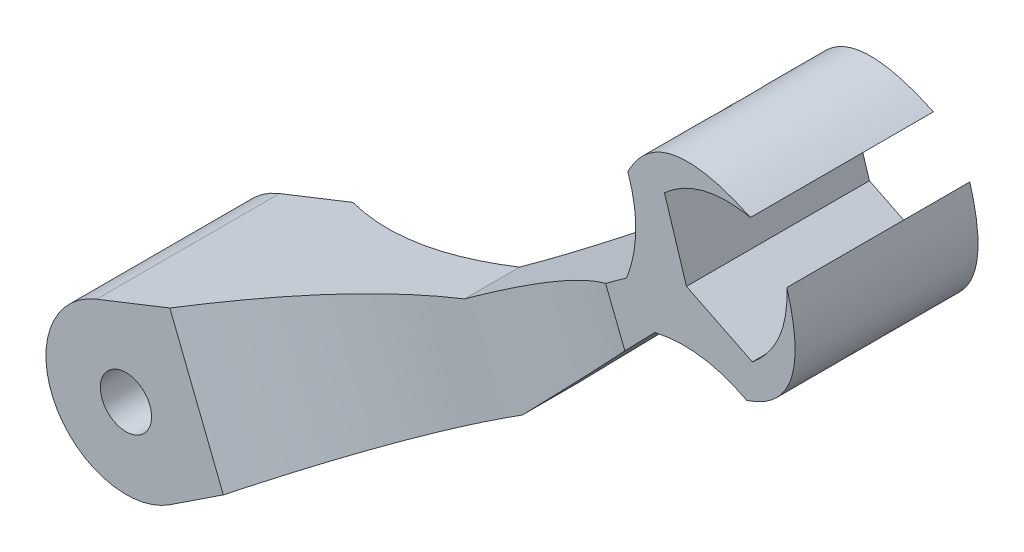
SolidWorks part; units mm, degrees
ref_plane "Front Plane" through (0, 0, 0) normal (0, 0, 1) x (1, 0, 0)
ref_plane "Top Plane" through (0, 0, 0) normal (0, 1, 0) x (1, 0, 0)
ref_plane "Right Plane" through (0, 0, 0) normal (1, 0, 0) x (0, 0, -1)
sketch "Sketch1" plane through (0, 0, 0) normal (0, 0, 1) x (1, 0, 0)
  line L0 (-6.5408, 16.5332) -> (60.9908, 43.2498)
  line L1 (9.7882, -14.8431) -> (74.0328, 27.5226)
  line L2 (74.0328, 27.5226) -> (117.5111, 72.1547)
  line L3 (60.9908, 43.2498) -> (111.2197, 79.4948)
  circle A0 centre (0, 0) radius 10.16
  arc A1 (-6.5408, 16.5332) -> (9.7882, -14.8431) centre (0, 0) ccw
  spline S0 degree 2 poles (111.2197, 79.4948) (115.1438, 89.5386) (111.4852, 100.0798) knots 0 0 0 1 1 1
  spline S1 degree 2 poles (111.4852, 100.0798) (118.6668, 114.3107) (138.7161, 104.879) knots 0 0 0 1 1 1
  spline S2 degree 1 poles (124.5067, 84.5172) (119.6143, 100.0798) knots 0 0 1 1
  spline S3 degree 2 poles (119.6143, 100.0798) (127.4642, 107.1326) (138.7161, 104.879) knots 0 0 0 1 1 1
  spline S4 degree 2 poles (137.8946, 69.2688) (153.0564, 74.1894) (146.8021, 95.4454) knots 0 0 0 1 1 1
  spline S5 degree 2 poles (139.1379, 77.3023) (147.3083, 83.9811) (146.8021, 95.4454) knots 0 0 0 1 1 1
  spline S6 degree 1 poles (124.5067, 84.5172) (139.1379, 77.3023) knots 0 0 1 1
  spline S7 degree 2 poles (117.5111, 72.1547) (128.037, 74.4966) (137.8946, 69.2688) knots 0 0 0 1 1 1
extrude "Boss-Extrude1" add sketch "Sketch1" against normal blind 20.32 and the other way blind 20.32
sketch "Sketch3" plane through (-6.5408, 16.5332, 0) normal (-0.3679, 0.9299, 0) x (0.9299, 0.3679, 0)
  line L0 (72.6243, 20.32) -> (0, 20.32) construction
  line L1 (72.6243, -20.32) -> (72.6243, 20.32) construction
  line L2 (17.521, 20.32) -> (69.3112, 80.4943)
  line L3 (69.3112, 80.4943) -> (134.5776, 24.5233)
  line L4 (-70.0562, 0) -> (70.0562, 0) construction
  line L5 (17.521, -20.32) -> (69.3112, -80.4943)
  line L6 (69.3112, -80.4943) -> (134.5776, -24.5233)
  spline S0 degree 2 poles (17.521, 20.32) (76.6425, -10.0424) (134.5776, 24.5233) knots 0 0 0 1 1 1
  spline S1 degree 2 poles (17.521, -20.32) (76.6425, 10.0424) (134.5776, -24.5233) knots 0 0 0 1 1 1
extrude "Cut-Extrude2" cut sketch "Sketch3" against normal blind 85.09 and the other way blind 85.09
sketch "Sketch4" plane through (0, 0, 0) normal (0, 0, 1) x (1, 0, 0)
  circle A0 centre (0, 0) radius 5.6901
  circle A1 centre (0, 0) radius 10.16
extrude "Boss-Extrude2" add sketch "Sketch4" along normal up to surface and the other way up to surface up to face at (10.16, 0, 20.32) other way up to face at (10.16, 0, -20.32)
